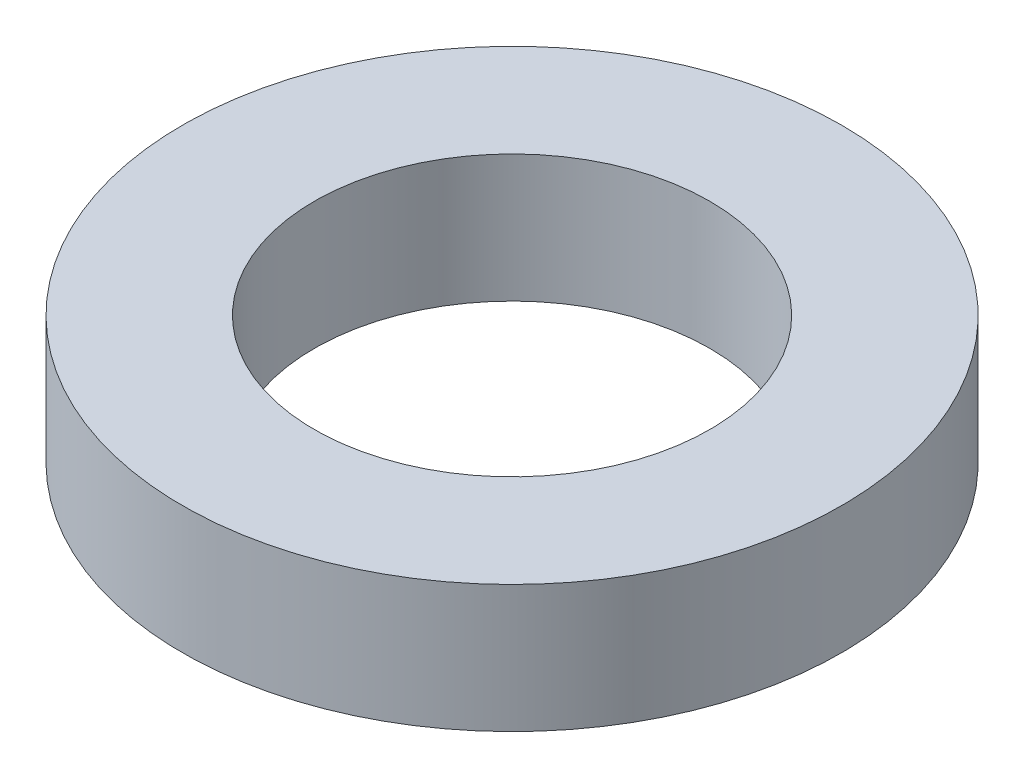
SolidWorks part; units mm, degrees
ref_plane "Front Plane" through (0, 0, 0) normal (0, 0, 1) x (1, 0, 0)
ref_plane "Top Plane" through (0, 0, 0) normal (0, 1, 0) x (1, 0, 0)
ref_plane "Right Plane" through (0, 0, 0) normal (1, 0, 0) x (0, 0, -1)
sketch "Sketch1" plane through (0, 0, 0) normal (0, 1, 0) x (1, 0, 0)
  circle A0 centre (0, 0) radius 75
  dimension "FLANGE_OD" = 150
extrude "Boss-Extrude1" add sketch "Sketch1" along normal blind 29
sketch "Sketch2" plane through (0, 0, 0) normal (0, 1, 0) x (1, 0, 0)
  circle A0 centre (0, 0) radius 45
  dimension "BORE_D" = 90
extrude "Cut-Extrude1" cut sketch "Sketch2" along normal through all
sketch "Sketch3" plane through (0, 29, 0) normal (0, 1, 0) x (1, 0, 0)
  circle A0 centre (0, 0) radius 27.2001 construction
  circle A1 centre (-27.2001, 0) radius 3.3662
  dimension "BOLT_D" = 6.7324
  dimension "BOLT_PCD" = 54.4003
extrude "Cut-Extrude2" cut sketch "Sketch3" against normal blind 25.7377 rebuild error yes
pattern_circular "CirPattern1" count 5 over 360 rebuild error yes
